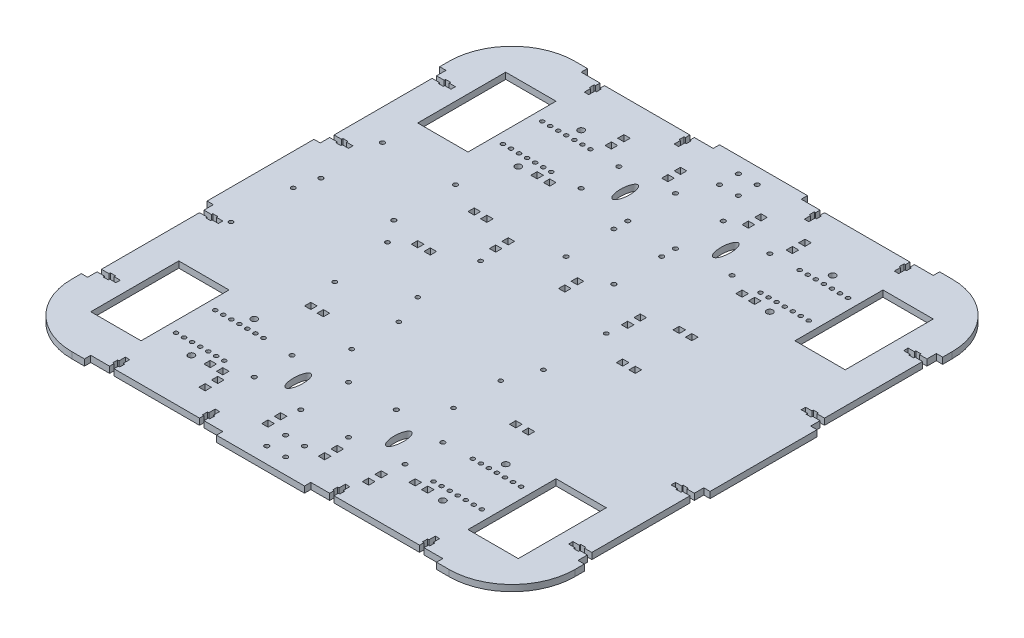
SolidWorks part; units mm, degrees
ref_plane "Front Plane" through (0, 0, 0) normal (0, 0, 1) x (1, 0, 0)
ref_plane "Top Plane" through (0, 0, 0) normal (0, 1, 0) x (1, 0, 0)
ref_plane "Right Plane" through (0, 0, 0) normal (1, 0, 0) x (0, 0, -1)
sketch "Sketch1" plane through (0, 0, 0) normal (0, 1, 0) x (1, 0, 0)
  line L0 (0, -1000) -> (0, 49000) construction
  line L1 (-170, 165) -> (-130, 165)
  line L2 (-170, 165) -> (-170, 95)
  line L3 (-170, 95) -> (-130, 95)
  line L4 (-130, 165) -> (-130, 95)
  line L5 (170, 95) -> (130, 95)
  line L6 (130, 165) -> (130, 95)
  line L7 (170, 165) -> (130, 165)
  line L8 (170, 165) -> (170, 95)
  line L9 (-1000, 0) -> (49000, 0) construction
  line L10 (-10, 190) -> (10, 190)
  line L11 (-10, 190) -> (-10, 170)
  line L12 (-10, 170) -> (10, 170)
  line L13 (10, 190) -> (10, 170)
  line L14 (-1010, 180) -> (48990, 180) construction
  line L15 (-1010, -180) -> (48990, -180) construction
  line L16 (0, 1000) -> (0, -49000) construction
  line L17 (-10, -170) -> (10, -170)
  line L18 (10, -190) -> (10, -170)
  line L19 (-10, -190) -> (10, -190)
  line L20 (-10, -190) -> (-10, -170)
  line L21 (170, -165) -> (170, -95)
  line L22 (-200, 200) -> (200, 200)
  line L23 (-200, 200) -> (-200, -200)
  line L24 (-200, -200) -> (200, -200)
  line L25 (200, 200) -> (200, -200)
  line L26 (170, -165) -> (130, -165)
  line L27 (130, -165) -> (130, -95)
  line L28 (170, -95) -> (130, -95)
  line L29 (-170, -95) -> (-130, -95)
  line L30 (-130, -165) -> (-130, -95)
  line L31 (-170, -165) -> (-130, -165)
  line L32 (-170, -165) -> (-170, -95)
  circle A0 centre (0, 0) radius 200 construction
  circle A1 centre (-7.5, 187.5) radius 1.75
  circle A2 centre (7.5, 187.5) radius 1.75
  circle A3 centre (7.5, 172.5) radius 1.75
  circle A4 centre (-7.5, 172.5) radius 1.75
  circle A5 centre (7.5, -187.5) radius 1.75
  circle A6 centre (-7.5, -187.5) radius 1.75
  circle A7 centre (-7.5, -172.5) radius 1.75
  circle A8 centre (7.5, -172.5) radius 1.75
  point P8 (-150, 165)
  point P19 (0, 190)
  point P22 (-10, 180)
  dimension "D1" = 400
  dimension "D7" = 3.5
  dimension "D2" = 40
  dimension "D3" = 70
  dimension "D4" = 150
  dimension "D5" = 20
  dimension "D6" = 180
  dimension "D8" = 2.5
  dimension "D9" = 2.5
  dimension "D10" = 35
extrude "Boss-Extrude2" add sketch "Sketch1" along normal blind 5 contours L25 L22 L23 L24 L1 L4 L3 L2 L7 L8 L5 L6 L10 L13 L12 L11 L19 L20 L17 L18 | L20 L19 L18 L17 A6 A5 A7 A8 | L13 L10 L11 L12 A2 A1 A3 A4 region at (0, 0, -180) region at (0, 0, 180) region at (0, 0, 0)
fillet "Fillet1" radius 50 4 edges at (200, 2.5, -200) (200, 2.5, 200) (-200, 2.5, 200) (-200, 2.5, -200)
sketch "Sketch2" plane through (0, 5, 0) normal (0, 1, 0) x (1, 0, 0)
  line L0 (-1094.0419, 130) -> (48905.9581, 130) construction
  line L1 (-130, 148.8) -> (-78.5, 148.8) construction
  line L2 (-130, 148.8) -> (-130, 111.2) construction
  line L3 (-130, 111.2) -> (-78.5, 111.2) construction
  line L4 (-78.5, 148.8) -> (-78.5, 111.2) construction
  line L5 (-130, 165) -> (-130, 95) construction
  line L6 (-170, 165) -> (-170, 95) construction
  line L7 (0, -1000) -> (0, 49000) construction
  line L8 (130, 111.2) -> (78.5, 111.2) construction
  line L9 (78.5, 148.8) -> (78.5, 111.2) construction
  line L10 (130, 148.8) -> (78.5, 148.8) construction
  line L11 (130, 148.8) -> (130, 111.2) construction
  line L12 (-1000, 0) -> (49000, 0) construction
  line L13 (130, -148.8) -> (130, -111.2) construction
  line L14 (130, -148.8) -> (78.5, -148.8) construction
  line L15 (78.5, -148.8) -> (78.5, -111.2) construction
  line L16 (130, -111.2) -> (78.5, -111.2) construction
  line L17 (-78.5, -148.8) -> (-78.5, -111.2) construction
  line L18 (-130, -111.2) -> (-78.5, -111.2) construction
  line L19 (-130, -148.8) -> (-130, -111.2) construction
  line L20 (-130, -148.8) -> (-78.5, -148.8) construction
  line L21 (-1094.0419, -130) -> (48905.9581, -130) construction
  circle A0 centre (-121.6, 145.6) radius 1.6
  circle A1 centre (-115.2, 145.6) radius 1.6
  circle A2 centre (-108.8, 145.6) radius 1.6
  circle A3 centre (-102.4, 145.6) radius 1.6
  circle A4 centre (-96, 145.6) radius 1.6
  circle A5 centre (-89.6, 145.6) radius 1.6
  circle A6 centre (-83.2, 145.6) radius 1.6
  circle A7 centre (-83.2, 114.4) radius 1.6
  circle A8 centre (-89.6, 114.4) radius 1.6
  circle A9 centre (-96, 114.4) radius 1.6
  circle A10 centre (-102.4, 114.4) radius 1.6
  circle A11 centre (-108.8, 114.4) radius 1.6
  circle A12 centre (-115.2, 114.4) radius 1.6
  circle A13 centre (-121.6, 114.4) radius 1.6
  circle A14 centre (83.2, 114.4) radius 1.6
  circle A15 centre (89.6, 114.4) radius 1.6
  circle A16 centre (96, 114.4) radius 1.6
  circle A17 centre (102.4, 114.4) radius 1.6
  circle A18 centre (108.8, 114.4) radius 1.6
  circle A19 centre (115.2, 114.4) radius 1.6
  circle A20 centre (121.6, 114.4) radius 1.6
  circle A21 centre (83.2, 145.6) radius 1.6
  circle A22 centre (89.6, 145.6) radius 1.6
  circle A23 centre (96, 145.6) radius 1.6
  circle A24 centre (102.4, 145.6) radius 1.6
  circle A25 centre (108.8, 145.6) radius 1.6
  circle A26 centre (115.2, 145.6) radius 1.6
  circle A27 centre (121.6, 145.6) radius 1.6
  circle A28 centre (121.6, -145.6) radius 1.6
  circle A29 centre (115.2, -145.6) radius 1.6
  circle A30 centre (108.8, -145.6) radius 1.6
  circle A31 centre (102.4, -145.6) radius 1.6
  circle A32 centre (96, -145.6) radius 1.6
  circle A33 centre (89.6, -145.6) radius 1.6
  circle A34 centre (83.2, -145.6) radius 1.6
  circle A35 centre (121.6, -114.4) radius 1.6
  circle A36 centre (115.2, -114.4) radius 1.6
  circle A37 centre (108.8, -114.4) radius 1.6
  circle A38 centre (102.4, -114.4) radius 1.6
  circle A39 centre (96, -114.4) radius 1.6
  circle A40 centre (89.6, -114.4) radius 1.6
  circle A41 centre (83.2, -114.4) radius 1.6
  circle A42 centre (-121.6, -114.4) radius 1.6
  circle A43 centre (-115.2, -114.4) radius 1.6
  circle A44 centre (-108.8, -114.4) radius 1.6
  circle A45 centre (-102.4, -114.4) radius 1.6
  circle A46 centre (-96, -114.4) radius 1.6
  circle A47 centre (-89.6, -114.4) radius 1.6
  circle A48 centre (-83.2, -114.4) radius 1.6
  circle A49 centre (-83.2, -145.6) radius 1.6
  circle A50 centre (-89.6, -145.6) radius 1.6
  circle A51 centre (-96, -145.6) radius 1.6
  circle A52 centre (-102.4, -145.6) radius 1.6
  circle A53 centre (-108.8, -145.6) radius 1.6
  circle A54 centre (-115.2, -145.6) radius 1.6
  circle A55 centre (-121.6, -145.6) radius 1.6
  point P9 (-130, 130)
  point P40 (-170, 130)
  dimension "D3" = 3.2
  dimension "D7" = 6.4
  dimension "D5" = 8.4
  dimension "D1" = 37.6
  dimension "D2" = 4.7
  dimension "D4" = 31.2
  dimension "D6" = 7
extrude "Cut-Extrude1" cut sketch "Sketch2" against normal blind 5
sketch "Sketch3" plane through (0, 5, 0) normal (0, 1, 0) x (1, 0, 0)
  line L0 (-150, -200) -> (150, -200) construction
  line L1 (-190, 3.34) -> (-88.4, 3.34) construction
  line L2 (-190, 3.34) -> (-190, -50) construction
  line L3 (-190, -50) -> (-88.4, -50) construction
  line L4 (-88.4, 3.34) -> (-88.4, -50) construction
  line L5 (-200, 150) -> (-200, -150) construction
  circle A0 centre (-176.03, -47.46) radius 1.65
  circle A1 centre (-174.76, 0.8) radius 1.65
  circle A2 centre (-93.48, -47.46) radius 1.65
  circle A3 centre (-99.83, 0.8) radius 1.65
  dimension "D5" = 3.3
  dimension "D8" = 3.3
  dimension "D9" = 96.52
  dimension "D10" = 90.17
  dimension "D1" = 101.6
  dimension "D2" = 53.34
  dimension "D3" = 13.97
  dimension "D4" = 2.54
  dimension "D6" = 15.24
  dimension "D7" = 50.8
  dimension "D11" = 150
  dimension "D12" = 10
extrude "Cut-Extrude2" cut sketch "Sketch3" against normal blind 10 contours A1 | A2 | L2 L1 L4 L3 | A0 | A3 region at (-174.76, 5, -0.8) region at (-93.48, 5, 47.46)
sketch "Sketch4" plane through (0, 5, 0) normal (0, 1, 0) x (1, 0, 0)
  line L0 (-19, 149) -> (19, 149) construction
  line L1 (-1149.7342, 130) -> (48850.2658, 130) construction
  line L2 (-22, 152) -> (22, 152) construction
  line L3 (-22, 152) -> (-22, 108) construction
  line L4 (-22, 108) -> (22, 108) construction
  line L5 (22, 152) -> (22, 108) construction
  line L6 (-19, 111) -> (19, 111) construction
  line L7 (-19, 100) -> (19, 100) construction
  line L8 (-1231.3219, 81) -> (48768.6781, 81) construction
  line L9 (-22, 103) -> (22, 103) construction
  line L10 (-22, 103) -> (-22, 59) construction
  line L11 (-22, 59) -> (22, 59) construction
  line L12 (22, 103) -> (22, 59) construction
  line L13 (-19, 62) -> (19, 62) construction
  line L14 (-19, -149) -> (19, -149) construction
  line L15 (-22, -152) -> (22, -152) construction
  line L16 (-130, 165) -> (-130, 95) construction
  line L17 (-150, 200) -> (150, 200) construction
  line L18 (22, -108) -> (22, -152) construction
  line L19 (-22, -108) -> (-22, -152) construction
  line L20 (-19, -111) -> (19, -111) construction
  line L21 (-22, -108) -> (22, -108) construction
  line L22 (-1022, -130) -> (48978, -130) construction
  line L23 (-130, -165) -> (-130, -95) construction
  circle A0 centre (-19, 149) radius 1.75
  circle A1 centre (19, 149) radius 1.75
  circle A2 centre (19, 111) radius 1.75
  circle A3 centre (-19, 111) radius 1.75
  circle A4 centre (-19, 100) radius 1.75
  circle A5 centre (19, 100) radius 1.75
  circle A6 centre (19, 62) radius 1.75
  circle A7 centre (-19, 62) radius 1.75
  circle A8 centre (-19, -149) radius 1.75
  circle A9 centre (19, -149) radius 1.75
  circle A10 centre (-19, -111) radius 1.75
  circle A11 centre (19, -111) radius 1.75
  point P9 (0, 149)
  point P10 (0, 152)
  point P14 (-22, 130)
  point P26 (0, 100)
  point P27 (0, 103)
  point P31 (-22, 81)
  point P38 (-130, 130)
  point P39 (0, 200)
  point P40 (0, 108)
  point P56 (-22, -130)
  point P58 (-130, -130)
  dimension "D1" = 3.5
  dimension "D5" = 3.5
  dimension "D2" = 38
  dimension "D3" = 44
  dimension "D4" = 38
  dimension "D6" = 38
  dimension "D7" = 44
  dimension "D8" = 38
  dimension "D9" = 5
  dimension "D10" = 2
extrude "Cut-Extrude3" cut sketch "Sketch4" against normal blind 10
sketch "Sketch5" plane through (0, 5, 0) normal (0, 1, 0) x (1, 0, 0)
  line L0 (-1136.3236, 43) -> (48863.6764, 43) construction
  line L1 (-174, 15) -> (-89, 15) construction
  line L2 (-174, 15) -> (-174, 71) construction
  line L3 (-174, 71) -> (-89, 71) construction
  line L4 (-89, 15) -> (-89, 71) construction
  line L5 (-180, 10) -> (-83, 10) construction
  line L6 (-180, 10) -> (-180, 76) construction
  line L7 (-180, 76) -> (-83, 76) construction
  line L8 (-83, 10) -> (-83, 76) construction
  line L9 (-200, 150) -> (-200, -150) construction
  line L10 (-150, -200) -> (150, -200) construction
  circle A0 centre (-170.5, 67.5) radius 1.75
  circle A1 centre (-112.5, 67.5) radius 1.75
  circle A2 centre (-112.5, 18.5) radius 1.75
  circle A3 centre (-170.5, 18.5) radius 1.75
  dimension "D4" = 3.5
  dimension "D5" = 3.5
  dimension "D1" = 56
  dimension "D2" = 85
  dimension "D3" = 58
  dimension "D6" = 3.5
  dimension "D7" = 49
  dimension "D8" = 3.5
  dimension "D9" = 5
  dimension "D10" = 5
  dimension "D11" = 6
  dimension "D12" = 6
  dimension "D13" = 20
  dimension "D14" = 210
extrude "Cut-Extrude4" cut sketch "Sketch5" against normal blind 10
sketch "Sketch6" plane through (0, 5, 0) normal (0, 1, 0) x (1, 0, 0)
  line L0 (-130, 165) -> (-130, 95) construction
  line L1 (0, -800) -> (0, 49200) construction
  line L2 (-150, 200) -> (150, 200) construction
  line L3 (-1200, 0) -> (48800, 0) construction
  line L4 (-200, 150) -> (-200, -150) construction
  ellipse E0 centre (-40, 130) end of major axis (-40, 140) minor radius 3.75
  ellipse E1 centre (40, 130) end of major axis (40, 140) minor radius 3.75
  ellipse E2 centre (40, -130) end of major axis (40, -140) minor radius 3.75
  ellipse E3 centre (-40, -130) end of major axis (-40, -140) minor radius 3.75
  point P13 (-130, 130)
  point P14 (-200, 0)
  point P26 (0, 200)
  dimension "D1" = 90
  dimension "D2" = 20
  dimension "D3" = 7.5
extrude "Cut-Extrude5" cut sketch "Sketch6" against normal blind 10
sketch "Sketch7" plane through (0, 5, 0) normal (0, 1, 0) x (1, 0, 0)
  line L0 (0, -1008.1082) -> (0, 48991.8918) construction
  line L1 (-53, 28) -> (53, 28) construction
  line L2 (-53, 28) -> (-53, -28) construction
  line L3 (-53, -28) -> (53, -28) construction
  line L4 (53, 28) -> (53, -28) construction
  line L5 (-53, 28) -> (-47, 28) construction
  line L6 (-53, 28) -> (-53, 22) construction
  line L7 (-53, 22) -> (-47, 22) construction
  line L8 (-47, 28) -> (-47, 22) construction
  line L9 (-1053, 0) -> (48947, 0) construction
  line L10 (-150, -200) -> (150, -200) construction
  line L11 (-200, 150) -> (-200, -150) construction
  circle A1 centre (-50, 25) radius 1.65
  circle A2 centre (50, 25) radius 1.65
  circle A3 centre (50, -25) radius 1.65
  circle A4 centre (-50, -25) radius 1.65
  point P10 (-50, 22)
  point P15 (-47, 25)
  point P16 (0, 28)
  point P17 (-53, 0)
  point P25 (0, -200)
  point P28 (-200, 0)
  dimension "D3" = 3.3
  dimension "D1" = 106
  dimension "D2" = 56
  dimension "D5" = 6
  dimension "D6" = 6
extrude "Cut-Extrude6" cut sketch "Sketch7" against normal blind 10
sketch "Sketch8" plane through (0, 5, 0) normal (0, 1, 0) x (1, 0, 0)
  line L0 (0, -1046.6714) -> (0, 48953.3286) construction
  line L1 (-43.5, -46.5) -> (43.5, -46.5) construction
  line L2 (-43.5, -46.5) -> (-43.5, -90) construction
  line L3 (-43.5, -90) -> (43.5, -90) construction
  line L4 (43.5, -46.5) -> (43.5, -90) construction
  line L5 (-43.5, -46.5) -> (-37.5, -46.5) construction
  line L6 (-43.5, -46.5) -> (-43.5, -52.5) construction
  line L7 (-43.5, -52.5) -> (-37.5, -52.5) construction
  line L8 (-37.5, -46.5) -> (-37.5, -52.5) construction
  line L9 (-1043.5, -68.25) -> (48956.5, -68.25) construction
  line L10 (37.5, -46.5) -> (37.5, -52.5) construction
  line L11 (43.5, -52.5) -> (37.5, -52.5) construction
  line L12 (-150, -200) -> (150, -200) construction
  circle A0 centre (-40.5, -49.5) radius 1.65
  circle A1 centre (40.5, -49.5) radius 1.65
  circle A2 centre (40.5, -87) radius 1.65
  circle A3 centre (-40.5, -87) radius 1.65
  point P10 (-40.5, -52.5)
  point P11 (-37.5, -49.5)
  point P15 (0, -46.5)
  point P17 (-43.5, -68.25)
  point P28 (0, -200)
  dimension "D3" = 3.3
  dimension "D1" = 87
  dimension "D2" = 6
  dimension "D4" = 43.5
  dimension "D5" = 110
extrude "Cut-Extrude7" cut sketch "Sketch8" against normal blind 5
sketch "Sketch10" plane through (0, 5, 0) normal (0, 1, 0) x (1, 0, 0)
  line L0 (-150, -200) -> (150, -200) construction
  line L1 (-125, -200) -> (-121.5, -200)
  line L2 (-125, -200) -> (-125, -191.5)
  line L3 (-125, -182.5) -> (-121.5, -182.5)
  line L4 (-121.5, -200) -> (-121.5, -191.5)
  line L6 (-121.5, -187.5) -> (-120.4, -187.5)
  line L7 (-126.1, -187.5) -> (-125, -187.5)
  line L8 (-126.1, -187.5) -> (-126.1, -191.5)
  line L9 (-126.1, -191.5) -> (-125, -191.5)
  line L10 (-120.4, -187.5) -> (-120.4, -191.5)
  line L11 (-121.5, -191.5) -> (-120.4, -191.5)
  line L12 (-125, -187.5) -> (-125, -182.5)
  line L13 (-121.5, -187.5) -> (-121.5, -182.5)
  line L14 (-125, -187.5) -> (-121.5, -187.5) construction
  line L15 (-121.5, -191.5) -> (-125, -191.5) construction
  line L16 (-53.5, -200) -> (-50, -200)
  line L17 (-50, -200) -> (-50, -191.5)
  line L18 (-50, -191.5) -> (-48.9, -191.5)
  line L19 (-48.9, -187.5) -> (-48.9, -191.5)
  line L20 (-50, -187.5) -> (-48.9, -187.5)
  line L21 (-50, -187.5) -> (-50, -182.5)
  line L22 (-53.5, -182.5) -> (-50, -182.5)
  line L23 (-53.5, -187.5) -> (-53.5, -182.5)
  line L24 (-54.6, -187.5) -> (-53.5, -187.5)
  line L25 (-54.6, -187.5) -> (-54.6, -191.5)
  line L26 (-54.6, -191.5) -> (-53.5, -191.5)
  line L27 (-53.5, -200) -> (-53.5, -191.5)
  line L28 (-50, -191.5) -> (-53.5, -191.5) construction
  line L29 (-53.5, -187.5) -> (-50, -187.5) construction
  line L30 (0, -1200) -> (0, 48800) construction
  line L31 (-200, 150) -> (-200, -150) construction
  line L32 (121.5, -191.5) -> (125, -191.5) construction
  line L33 (125, -187.5) -> (121.5, -187.5) construction
  line L34 (125, -200) -> (125, -191.5)
  line L35 (126.1, -191.5) -> (125, -191.5)
  line L36 (126.1, -187.5) -> (126.1, -191.5)
  line L37 (126.1, -187.5) -> (125, -187.5)
  line L38 (125, -187.5) -> (125, -182.5)
  line L39 (125, -182.5) -> (121.5, -182.5)
  line L40 (121.5, -187.5) -> (121.5, -182.5)
  line L41 (121.5, -187.5) -> (120.4, -187.5)
  line L42 (120.4, -187.5) -> (120.4, -191.5)
  line L43 (121.5, -191.5) -> (120.4, -191.5)
  line L44 (121.5, -200) -> (121.5, -191.5)
  line L45 (125, -200) -> (121.5, -200)
  line L46 (53.5, -187.5) -> (50, -187.5) construction
  line L47 (50, -191.5) -> (53.5, -191.5) construction
  line L48 (53.5, -200) -> (53.5, -191.5)
  line L49 (54.6, -191.5) -> (53.5, -191.5)
  line L50 (54.6, -187.5) -> (54.6, -191.5)
  line L51 (54.6, -187.5) -> (53.5, -187.5)
  line L52 (53.5, -187.5) -> (53.5, -182.5)
  line L53 (53.5, -182.5) -> (50, -182.5)
  line L54 (50, -187.5) -> (50, -182.5)
  line L55 (50, -187.5) -> (48.9, -187.5)
  line L56 (48.9, -187.5) -> (48.9, -191.5)
  line L57 (50, -191.5) -> (48.9, -191.5)
  line L58 (50, -200) -> (50, -191.5)
  line L59 (53.5, -200) -> (50, -200)
  line L60 (-1000, 0) -> (49000, 0) construction
  line L61 (125, 200) -> (121.5, 200)
  line L62 (121.5, 200) -> (121.5, 191.5)
  line L63 (121.5, 191.5) -> (120.4, 191.5)
  line L64 (120.4, 187.5) -> (120.4, 191.5)
  line L65 (121.5, 187.5) -> (120.4, 187.5)
  line L66 (121.5, 187.5) -> (121.5, 182.5)
  line L67 (125, 182.5) -> (121.5, 182.5)
  line L68 (125, 187.5) -> (125, 182.5)
  line L69 (126.1, 187.5) -> (125, 187.5)
  line L70 (126.1, 187.5) -> (126.1, 191.5)
  line L71 (126.1, 191.5) -> (125, 191.5)
  line L72 (125, 200) -> (125, 191.5)
  line L73 (53.5, 200) -> (50, 200)
  line L74 (50, 200) -> (50, 191.5)
  line L75 (50, 191.5) -> (48.9, 191.5)
  line L76 (48.9, 187.5) -> (48.9, 191.5)
  line L77 (50, 187.5) -> (48.9, 187.5)
  line L78 (50, 187.5) -> (50, 182.5)
  line L79 (53.5, 182.5) -> (50, 182.5)
  line L80 (53.5, 187.5) -> (53.5, 182.5)
  line L81 (54.6, 187.5) -> (53.5, 187.5)
  line L82 (54.6, 187.5) -> (54.6, 191.5)
  line L83 (54.6, 191.5) -> (53.5, 191.5)
  line L84 (53.5, 200) -> (53.5, 191.5)
  line L85 (-53.5, 200) -> (-53.5, 191.5)
  line L86 (-54.6, 191.5) -> (-53.5, 191.5)
  line L87 (-54.6, 187.5) -> (-54.6, 191.5)
  line L88 (-54.6, 187.5) -> (-53.5, 187.5)
  line L89 (-53.5, 187.5) -> (-53.5, 182.5)
  line L90 (-53.5, 182.5) -> (-50, 182.5)
  line L91 (-50, 187.5) -> (-50, 182.5)
  line L92 (-50, 187.5) -> (-48.9, 187.5)
  line L93 (-48.9, 187.5) -> (-48.9, 191.5)
  line L94 (-50, 191.5) -> (-48.9, 191.5)
  line L95 (-50, 200) -> (-50, 191.5)
  line L96 (-53.5, 200) -> (-50, 200)
  line L97 (-125, 200) -> (-125, 191.5)
  line L98 (-126.1, 191.5) -> (-125, 191.5)
  line L99 (-126.1, 187.5) -> (-126.1, 191.5)
  line L100 (-126.1, 187.5) -> (-125, 187.5)
  line L101 (-125, 187.5) -> (-125, 182.5)
  line L102 (-125, 182.5) -> (-121.5, 182.5)
  line L103 (-121.5, 187.5) -> (-121.5, 182.5)
  line L104 (-121.5, 187.5) -> (-120.4, 187.5)
  line L105 (-120.4, 187.5) -> (-120.4, 191.5)
  line L106 (-121.5, 191.5) -> (-120.4, 191.5)
  line L107 (-121.5, 200) -> (-121.5, 191.5)
  line L108 (-125, 200) -> (-121.5, 200)
  point P11 (-123.25, -200)
  point P15 (-123.25, -191.5)
  point P16 (-123.25, -187.5)
  point P17 (-123.25, -182.5)
  point P33 (0, -200)
  dimension "D1" = 3.5
  dimension "D2" = 5.7
  dimension "D3" = 5
  dimension "D4" = 4
  dimension "D5" = 1.1
  dimension "D7" = 75
  dimension "D8" = 50
  dimension "D9" = 17.5
  dimension "D6" = 2
extrude "Cut-Extrude8" cut sketch "Sketch10" against normal blind 10
sketch "Sketch11" plane through (0, 5, 0) normal (0, 1, 0) x (1, 0, 0)
  line L0 (-150, -200) -> (-125, -200) construction
  line L1 (-140, -200) -> (-35, -200)
  line L2 (-140, -200) -> (-140, -195)
  line L3 (-140, -195) -> (-35, -195)
  line L4 (-35, -200) -> (-35, -195)
  line L5 (-50, -200) -> (-50, -191.5) construction
  line L6 (-125, -191.5) -> (-125, -200) construction
  line L7 (0, -1200) -> (0, 48800) construction
  line L8 (-50, -200) -> (50, -200) construction
  line L9 (-1200, 0) -> (48800, 0) construction
  line L10 (-200, 150) -> (-200, -150) construction
  line L11 (140, -195) -> (35, -195)
  line L12 (35, -200) -> (35, -195)
  line L13 (140, -200) -> (35, -200)
  line L14 (140, -200) -> (140, -195)
  line L15 (140, 200) -> (140, 195)
  line L16 (140, 200) -> (35, 200)
  line L17 (35, 200) -> (35, 195)
  line L18 (140, 195) -> (35, 195)
  line L19 (-140, 195) -> (-35, 195)
  line L20 (-35, 200) -> (-35, 195)
  line L21 (-140, 200) -> (-35, 200)
  line L22 (-140, 200) -> (-140, 195)
  point P15 (0, -200)
  point P20 (-200, 0)
  dimension "D1" = 5
  dimension "D2" = 15
  dimension "D3" = 15
extrude "Cut-Extrude9" cut sketch "Sketch11" against normal blind 10
sketch "Sketch12" plane through (0, 5, 0) normal (0, 1, 0) x (1, 0, 0)
  line L0 (-200, 150) -> (-200, -150) construction
  line L1 (-200, 135) -> (-189, 135)
  line L2 (-200, 135) -> (-200, 131.5)
  line L3 (-200, 131.5) -> (-189, 131.5)
  line L4 (-180, 135) -> (-180, 131.5)
  line L5 (-200, 53.5) -> (-189, 53.5)
  line L6 (-189, 131.5) -> (-189, 130.4)
  line L7 (-189, 136.1) -> (-185, 136.1)
  line L8 (-189, 136.1) -> (-189, 135)
  line L9 (-189, 130.4) -> (-185, 130.4)
  line L10 (-185, 136.1) -> (-185, 135)
  line L11 (-185, 131.5) -> (-185, 130.4)
  line L12 (-185, 135) -> (-180, 135)
  line L13 (-185, 131.5) -> (-180, 131.5)
  line L14 (-189, 135) -> (-189, 131.5) construction
  line L15 (-185, 131.5) -> (-185, 135) construction
  line L16 (-189, 54.6) -> (-189, 53.5)
  line L17 (-189, 54.6) -> (-185, 54.6)
  line L18 (-185, 54.6) -> (-185, 53.5)
  line L19 (-185, 53.5) -> (-180, 53.5)
  line L20 (-180, 53.5) -> (-180, 50)
  line L21 (-185, 50) -> (-180, 50)
  line L22 (-185, 50) -> (-185, 48.9)
  line L23 (-189, 48.9) -> (-185, 48.9)
  line L24 (-189, 50) -> (-189, 48.9)
  line L25 (-200, 50) -> (-189, 50)
  line L26 (-200, 53.5) -> (-200, 50)
  line L27 (-1200, 0) -> (48800, 0) construction
  line L28 (-200, -53.5) -> (-200, -50)
  line L29 (-200, -50) -> (-189, -50)
  line L30 (-189, -50) -> (-189, -48.9)
  line L31 (-189, -48.9) -> (-185, -48.9)
  line L32 (-185, -50) -> (-185, -48.9)
  line L33 (-185, -50) -> (-180, -50)
  line L34 (-180, -53.5) -> (-180, -50)
  line L35 (-185, -53.5) -> (-180, -53.5)
  line L36 (-185, -54.6) -> (-185, -53.5)
  line L37 (-189, -54.6) -> (-185, -54.6)
  line L38 (-189, -54.6) -> (-189, -53.5)
  line L39 (-200, -53.5) -> (-189, -53.5)
  line L40 (-200, -135) -> (-200, -131.5)
  line L41 (-200, -131.5) -> (-189, -131.5)
  line L42 (-189, -131.5) -> (-189, -130.4)
  line L43 (-189, -130.4) -> (-185, -130.4)
  line L44 (-185, -131.5) -> (-185, -130.4)
  line L45 (-185, -131.5) -> (-180, -131.5)
  line L46 (-180, -135) -> (-180, -131.5)
  line L47 (-185, -135) -> (-180, -135)
  line L48 (-185, -136.1) -> (-185, -135)
  line L49 (-189, -136.1) -> (-185, -136.1)
  line L50 (-189, -136.1) -> (-189, -135)
  line L51 (-200, -135) -> (-189, -135)
  line L52 (0, -1200) -> (0, 48800) construction
  line L53 (-35, -200) -> (35, -200) construction
  line L54 (200, -135) -> (189, -135)
  line L55 (189, -136.1) -> (189, -135)
  line L56 (189, -136.1) -> (185, -136.1)
  line L57 (185, -136.1) -> (185, -135)
  line L58 (185, -135) -> (180, -135)
  line L59 (180, -135) -> (180, -131.5)
  line L60 (185, -131.5) -> (180, -131.5)
  line L61 (185, -131.5) -> (185, -130.4)
  line L62 (189, -130.4) -> (185, -130.4)
  line L63 (189, -131.5) -> (189, -130.4)
  line L64 (200, -131.5) -> (189, -131.5)
  line L65 (200, -135) -> (200, -131.5)
  line L66 (200, -53.5) -> (189, -53.5)
  line L67 (189, -54.6) -> (189, -53.5)
  line L68 (189, -54.6) -> (185, -54.6)
  line L69 (185, -54.6) -> (185, -53.5)
  line L70 (185, -53.5) -> (180, -53.5)
  line L71 (180, -53.5) -> (180, -50)
  line L72 (185, -50) -> (180, -50)
  line L73 (185, -50) -> (185, -48.9)
  line L74 (189, -48.9) -> (185, -48.9)
  line L75 (189, -50) -> (189, -48.9)
  line L76 (200, -50) -> (189, -50)
  line L77 (200, -53.5) -> (200, -50)
  line L78 (200, 53.5) -> (200, 50)
  line L79 (200, 50) -> (189, 50)
  line L80 (189, 50) -> (189, 48.9)
  line L81 (189, 48.9) -> (185, 48.9)
  line L82 (185, 50) -> (185, 48.9)
  line L83 (185, 50) -> (180, 50)
  line L84 (180, 53.5) -> (180, 50)
  line L85 (185, 53.5) -> (180, 53.5)
  line L86 (185, 54.6) -> (185, 53.5)
  line L87 (189, 54.6) -> (185, 54.6)
  line L88 (189, 54.6) -> (189, 53.5)
  line L89 (200, 53.5) -> (189, 53.5)
  line L90 (200, 135) -> (200, 131.5)
  line L91 (200, 131.5) -> (189, 131.5)
  line L92 (189, 131.5) -> (189, 130.4)
  line L93 (189, 130.4) -> (185, 130.4)
  line L94 (185, 131.5) -> (185, 130.4)
  line L95 (185, 131.5) -> (180, 131.5)
  line L96 (180, 135) -> (180, 131.5)
  line L97 (185, 135) -> (180, 135)
  line L98 (185, 136.1) -> (185, 135)
  line L99 (189, 136.1) -> (185, 136.1)
  line L100 (189, 136.1) -> (189, 135)
  line L101 (200, 135) -> (189, 135)
  point P31 (-200, 0)
  point P60 (0, -200)
  dimension "D1" = 20
  dimension "D2" = 3.5
  dimension "D3" = 5.7
  dimension "D4" = 5
  dimension "D5" = 4
  dimension "D6" = 15
  dimension "D7" = 1.1
  dimension "D9" = 50
  dimension "D8" = 2
extrude "Cut-Extrude10" cut sketch "Sketch12" against normal blind 5
sketch "Sketch13" plane through (0, 5, 0) normal (0, 1, 0) x (1, 0, 0)
  line L0 (-200, 150) -> (-200, 135) construction
  line L1 (-200, 142.5) -> (-195, 142.5)
  line L2 (-200, 142.5) -> (-200, 42.5)
  line L3 (-200, 42.5) -> (-195, 42.5)
  line L4 (-195, 142.5) -> (-195, 42.5)
  line L6 (-200, 50) -> (-189, 50) construction
  line L7 (-1200, 0) -> (48800, 0) construction
  line L8 (-200, 50) -> (-200, -50) construction
  line L9 (0, -800) -> (0, 49200) construction
  line L10 (-35, 200) -> (35, 200) construction
  line L11 (-200, -42.5) -> (-195, -42.5)
  line L12 (-195, -142.5) -> (-195, -42.5)
  line L13 (-200, -142.5) -> (-195, -142.5)
  line L14 (-200, -142.5) -> (-200, -42.5)
  line L15 (0, 800) -> (0, -49200) construction
  line L16 (200, -142.5) -> (200, -42.5)
  line L17 (200, -142.5) -> (195, -142.5)
  line L18 (195, -142.5) -> (195, -42.5)
  line L19 (200, -42.5) -> (195, -42.5)
  line L20 (200, 42.5) -> (195, 42.5)
  line L21 (195, 142.5) -> (195, 42.5)
  line L22 (200, 142.5) -> (195, 142.5)
  line L23 (200, 142.5) -> (200, 42.5)
  point P13 (-200, 0)
  point P18 (0, 200)
  dimension "D1" = 7.5
  dimension "D2" = 5
extrude "Cut-Extrude11" cut sketch "Sketch13" against normal blind 5
sketch "Sketch14" plane through (0, 5, 0) normal (0, 1, 0) x (1, 0, 0)
  line L0 (34, 164) -> (29, 164)
  line L1 (34, 154) -> (29, 154)
  line L2 (34, 154) -> (34, 159)
  line L3 (34, 159) -> (29, 159)
  line L4 (29, 154) -> (29, 159)
  line L5 (34, 164) -> (34, 169)
  line L6 (34, 169) -> (29, 169)
  line L7 (29, 164) -> (29, 169)
  line L8 (69, 164) -> (64, 164)
  line L9 (69, 154) -> (64, 154)
  line L10 (69, 154) -> (69, 159)
  line L11 (69, 159) -> (64, 159)
  line L12 (64, 154) -> (64, 159)
  line L13 (69, 164) -> (69, 169)
  line L14 (69, 169) -> (64, 169)
  line L15 (64, 164) -> (64, 169)
  line L16 (5, 47) -> (0, 47)
  line L17 (5, 37) -> (0, 37)
  line L18 (5, 37) -> (5, 42)
  line L19 (5, 42) -> (0, 42)
  line L20 (0, 37) -> (0, 42)
  line L21 (5, 47) -> (5, 52)
  line L22 (5, 52) -> (0, 52)
  line L23 (0, 47) -> (0, 52)
  line L24 (55, 47) -> (50, 47)
  line L25 (55, 37) -> (50, 37)
  line L26 (55, 37) -> (55, 42)
  line L27 (55, 42) -> (50, 42)
  line L28 (50, 37) -> (50, 42)
  line L29 (55, 47) -> (55, 52)
  line L30 (55, 52) -> (50, 52)
  line L31 (50, 47) -> (50, 52)
  line L32 (25, -164) -> (20, -164)
  line L33 (25, -174) -> (20, -174)
  line L34 (25, -174) -> (25, -169)
  line L35 (25, -169) -> (20, -169)
  line L36 (20, -174) -> (20, -169)
  line L37 (25, -164) -> (25, -159)
  line L38 (25, -159) -> (20, -159)
  line L39 (20, -164) -> (20, -159)
  line L40 (60, -164) -> (55, -164)
  line L41 (60, -174) -> (55, -174)
  line L42 (60, -174) -> (60, -169)
  line L43 (60, -169) -> (55, -169)
  line L44 (55, -174) -> (55, -169)
  line L45 (60, -164) -> (60, -159)
  line L46 (60, -159) -> (55, -159)
  line L47 (55, -164) -> (55, -159)
  line L48 (-30, 164) -> (-35, 164)
  line L49 (-30, 154) -> (-35, 154)
  line L50 (-30, 154) -> (-30, 159)
  line L51 (-30, 159) -> (-35, 159)
  line L52 (-35, 154) -> (-35, 159)
  line L53 (-30, 164) -> (-30, 169)
  line L54 (-30, 169) -> (-35, 169)
  line L55 (-35, 164) -> (-35, 169)
  line L56 (-50, 47) -> (-55, 47)
  line L57 (-50, 37) -> (-55, 37)
  line L58 (-50, 37) -> (-50, 42)
  line L59 (-50, 42) -> (-55, 42)
  line L60 (-55, 37) -> (-55, 42)
  line L61 (-50, 47) -> (-50, 52)
  line L62 (-50, 52) -> (-55, 52)
  line L63 (-55, 47) -> (-55, 52)
  line L64 (-20, -164) -> (-25, -164)
  line L65 (-20, -174) -> (-25, -174)
  line L66 (-20, -174) -> (-20, -169)
  line L67 (-20, -169) -> (-25, -169)
  line L68 (-25, -174) -> (-25, -169)
  line L69 (-20, -164) -> (-20, -159)
  line L70 (-20, -159) -> (-25, -159)
  line L71 (-25, -164) -> (-25, -159)
  line L72 (19, 62) -> (-19, 62) construction
  line L73 (19, 149) -> (-19, 149) construction
  line L74 (-75, 164) -> (-80, 164)
  line L75 (-75, 154) -> (-80, 154)
  line L76 (-75, 154) -> (-75, 159)
  line L77 (-75, 159) -> (-80, 159)
  line L78 (-80, 154) -> (-80, 159)
  line L79 (-75, 164) -> (-75, 169)
  line L80 (-75, 169) -> (-80, 169)
  line L81 (-80, 164) -> (-80, 169)
  line L82 (19, -149) -> (-19, -149) construction
  line L83 (-70, -164) -> (-75, -164)
  line L84 (-70, -174) -> (-75, -174)
  line L85 (-70, -174) -> (-70, -169)
  line L86 (-70, -169) -> (-75, -169)
  line L87 (-75, -174) -> (-75, -169)
  line L88 (-70, -164) -> (-70, -159)
  line L89 (-70, -159) -> (-75, -159)
  line L90 (-75, -164) -> (-75, -159)
  line L91 (79, -156) -> (74, -156)
  line L92 (89, -156) -> (84, -156)
  line L93 (89, -156) -> (89, -151)
  line L94 (89, -151) -> (84, -151)
  line L95 (84, -156) -> (84, -151)
  line L96 (79, -156) -> (79, -151)
  line L97 (79, -151) -> (74, -151)
  line L98 (74, -156) -> (74, -151)
  line L99 (79, -76) -> (74, -76)
  line L100 (89, -76) -> (84, -76)
  line L101 (89, -76) -> (89, -71)
  line L102 (89, -71) -> (84, -71)
  line L103 (84, -76) -> (84, -71)
  line L104 (79, -76) -> (79, -71)
  line L105 (79, -71) -> (74, -71)
  line L106 (74, -76) -> (74, -71)
  line L107 (79, 9) -> (74, 9)
  line L108 (89, 9) -> (84, 9)
  line L109 (89, 9) -> (89, 14)
  line L110 (89, 14) -> (84, 14)
  line L111 (84, 9) -> (84, 14)
  line L112 (79, 9) -> (79, 14)
  line L113 (79, 14) -> (74, 14)
  line L114 (74, 9) -> (74, 14)
  line L115 (79, 54) -> (74, 54)
  line L116 (89, 54) -> (84, 54)
  line L117 (89, 54) -> (89, 59)
  line L118 (89, 59) -> (84, 59)
  line L119 (84, 54) -> (84, 59)
  line L120 (79, 54) -> (79, 59)
  line L121 (79, 59) -> (74, 59)
  line L122 (74, 54) -> (74, 59)
  line L123 (79, 104) -> (74, 104)
  line L124 (89, 104) -> (84, 104)
  line L125 (89, 104) -> (89, 109)
  line L126 (89, 109) -> (84, 109)
  line L127 (84, 104) -> (84, 109)
  line L128 (79, 104) -> (79, 109)
  line L129 (79, 109) -> (74, 109)
  line L130 (74, 104) -> (74, 109)
  line L131 (0, -1200) -> (0, 48800) construction
  line L132 (-35, -200) -> (35, -200) construction
  line L133 (-79, 104) -> (-79, 109)
  line L134 (-79, 109) -> (-74, 109)
  line L135 (-74, 104) -> (-74, 109)
  line L136 (-79, 104) -> (-74, 104)
  line L137 (-89, 104) -> (-89, 109)
  line L138 (-89, 109) -> (-84, 109)
  line L139 (-84, 104) -> (-84, 109)
  line L140 (-89, 104) -> (-84, 104)
  line L141 (-79, 54) -> (-79, 59)
  line L142 (-79, 59) -> (-74, 59)
  line L143 (-74, 54) -> (-74, 59)
  line L144 (-79, 54) -> (-74, 54)
  line L145 (-89, 54) -> (-89, 59)
  line L146 (-89, 59) -> (-84, 59)
  line L147 (-84, 54) -> (-84, 59)
  line L148 (-89, 54) -> (-84, 54)
  line L149 (-79, 9) -> (-79, 14)
  line L150 (-79, 14) -> (-74, 14)
  line L151 (-74, 9) -> (-74, 14)
  line L152 (-79, 9) -> (-74, 9)
  line L153 (-89, 9) -> (-89, 14)
  line L154 (-89, 14) -> (-84, 14)
  line L155 (-84, 9) -> (-84, 14)
  line L156 (-89, 9) -> (-84, 9)
  line L157 (-79, -76) -> (-79, -71)
  line L158 (-79, -71) -> (-74, -71)
  line L159 (-74, -76) -> (-74, -71)
  line L160 (-79, -76) -> (-74, -76)
  line L161 (-89, -76) -> (-89, -71)
  line L162 (-89, -71) -> (-84, -71)
  line L163 (-84, -76) -> (-84, -71)
  line L164 (-89, -76) -> (-84, -76)
  line L165 (-79, -156) -> (-79, -151)
  line L166 (-79, -151) -> (-74, -151)
  line L167 (-74, -156) -> (-74, -151)
  line L168 (-79, -156) -> (-74, -156)
  line L169 (-89, -156) -> (-89, -151)
  line L170 (-89, -151) -> (-84, -151)
  line L171 (-84, -156) -> (-84, -151)
  line L172 (-89, -156) -> (-84, -156)
  circle A0 centre (19, 149) radius 1.75 construction
  point P78 (0, 49.5)
  point P79 (0, 62)
  point P83 (0, 149)
  point P84 (0, -149)
  point P151 (0, -200)
  dimension "D20" = 10
  dimension "D1" = 5
  dimension "D2" = 5
  dimension "D3" = 5
  dimension "D4" = 5
  dimension "D5" = 5
  dimension "D6" = 5
  dimension "D7" = 5
  dimension "D8" = 5
  dimension "D9" = 5
  dimension "D10" = 5
  dimension "D11" = 5
  dimension "D12" = 5
  dimension "D13" = 5
  dimension "D14" = 5
  dimension "D15" = 5
  dimension "D16" = 5
  dimension "D17" = 5
  dimension "D18" = 5
  dimension "D19" = 30
  dimension "D21" = 10
  dimension "D22" = 10
  dimension "D23" = 45
  dimension "D24" = 50
  dimension "D25" = 30
  dimension "D26" = 5
  dimension "D27" = 5
  dimension "D28" = 40
  dimension "D29" = 20
  dimension "D30" = 10
  dimension "D31" = 30
  dimension "D32" = 20
  dimension "D33" = 5
  dimension "D34" = 5
  dimension "D35" = 45
  dimension "D36" = 5
  dimension "D37" = 5
  dimension "D38" = 5
  dimension "D39" = 5
  dimension "D40" = 5
  dimension "D41" = 5
  dimension "D42" = 5
  dimension "D43" = 5
  dimension "D44" = 5
  dimension "D45" = 5
  dimension "D46" = 5
  dimension "D47" = 45
  dimension "D48" = 45
  dimension "D49" = 40
  dimension "D50" = 80
  dimension "D51" = 75
extrude "Cut-Extrude12" cut sketch "Sketch14" against normal blind 10
sketch "Sketch15" plane through (0, 5, 0) normal (0, 1, 0) x (1, 0, 0)
  line L0 (-1130, 130) -> (48870, 130) construction
  line L1 (-130, 165) -> (-130, 95) construction
  line L2 (0, -800) -> (0, 49200) construction
  line L3 (-35, 200) -> (35, 200) construction
  line L4 (-1200, 0) -> (48800, 0) construction
  line L5 (-200, 42.5) -> (-200, -42.5) construction
  line L6 (1200, 0) -> (-48800, 0) construction
  circle A0 centre (-100, 105) radius 2.5
  circle A1 centre (-100, 155) radius 2.5
  circle A2 centre (100, 155) radius 2.5
  circle A3 centre (100, 105) radius 2.5
  circle A4 centre (100, -105) radius 2.5
  circle A5 centre (100, -155) radius 2.5
  circle A6 centre (-100, -155) radius 2.5
  circle A7 centre (-100, -105) radius 2.5
  point P7 (-130, 130)
  point P14 (0, 200)
  point P19 (-200, 0)
  dimension "D1" = 5
  dimension "D2" = 25
  dimension "D3" = 30
extrude "Cut-Extrude13" cut sketch "Sketch15" against normal blind 10
sketch "Sketch16" plane through (0, 5, 0) normal (0, 1, 0) x (1, 0, 0)
  line L1 (-60, 145) -> (-60, 115) construction
  line L2 (-130, 165) -> (-130, 95) construction
  line L3 (0, -800) -> (0, 49200) construction
  line L4 (-35, 200) -> (35, 200) construction
  line L5 (-1200, 0) -> (48800, 0) construction
  line L6 (-200, 42.5) -> (-200, -42.5) construction
  circle A0 centre (-60, 145) radius 1.75
  circle A1 centre (-60, 115) radius 1.75
  circle A2 centre (60, 115) radius 1.75
  circle A3 centre (60, 145) radius 1.75
  circle A4 centre (60, -115) radius 1.75
  circle A5 centre (60, -145) radius 1.75
  circle A6 centre (-60, -145) radius 1.75
  circle A7 centre (-60, -115) radius 1.75
  ellipse E0 centre (-40, 130) end of major axis (-40, 140) minor radius 3.75 construction
  point P10 (-130, 130)
  point P13 (-60, 130)
  point P19 (0, 200)
  point P24 (-200, 0)
  dimension "D1" = 3.5
  dimension "D2" = 30
  dimension "D3" = 20
extrude "Cut-Extrude14" cut sketch "Sketch16" against normal blind 10
